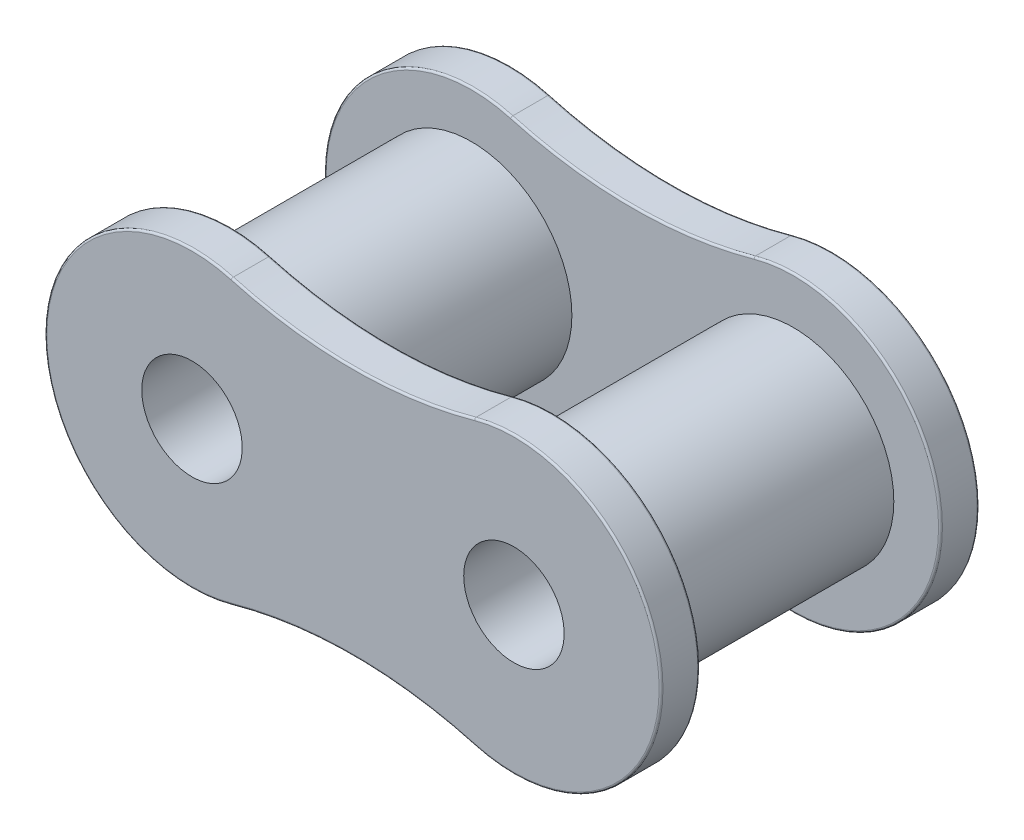
SolidWorks part; units mm, degrees
ref_plane "Front Plane" through (0, 0, 0) normal (0, 0, 1) x (1, 0, 0)
ref_plane "Top Plane" through (0, 0, 0) normal (0, 1, 0) x (1, 0, 0)
ref_plane "Right Plane" through (0, 0, 0) normal (1, 0, 0) x (0, 0, -1)
sketch "Sketch2" plane through (0, 0, 0) normal (0, 0, 1) x (1, 0, 0)
  line L0 (-6.35, 0) -> (6.35, 0) construction
  line L1 (0, -4.9333) -> (0, 4.9333) construction
  circle A0 centre (-6.35, 0) radius 1.9812
  circle A1 centre (-6.35, 0) radius 3.9624
  circle A2 centre (-6.35, 0) radius 5.8039
  circle A11 centre (6.35, 0) radius 1.9812
  circle A12 centre (6.35, 0) radius 3.9624
  circle A13 centre (6.35, 0) radius 5.8039
  point P3 (0, 0)
  point P4 (0, 0)
  point P8 (0, 0)
  point P18 (0, 0)
  point P21 (0, 4.9333)
  point P22 (0, -4.9333)
  point P23 (0, 0)
  dimension "D1" = 11.6078
  dimension "D2" = 3.9624
  dimension "D3" = 7.9248
  dimension "D4" = 12.7
  dimension "D5" = 9.8666
extrude "Boss-Extrude1" add sketch "Sketch2" against normal blind 10 from offset 5.5118 contours A1 A0 | A12 A11 region at (-10.2003, 0, 0) region at (2.4997, 0, 0)
fillet "Fillet1" radius 0.1585 2 edges at (-2.3876, 0, -4.4882) (-2.3876, 0, 5.5118)
fillet "Fillet2" radius 0.1585 2 edges at (10.3124, 0, -4.4882) (10.3124, 0, 5.5118)
sketch "Sketch3" plane through (0, 0, 0) normal (0, 0, 1) x (1, 0, 0)
  line L0 (-6.35, 0) -> (6.35, 0) construction
  line L1 (0, -4.9333) -> (0, 4.9333) construction
  arc A2 (-4.7879, 5.5897) -> (-4.7879, -5.5897) centre (-6.35, 0) ccw
  arc A9 (4.7879, 5.5897) -> (-4.7879, 5.5897) centre (0, 22.723) cw
  arc A10 (4.7879, -5.5897) -> (-4.7879, -5.5897) centre (0, -22.723) ccw
  arc A13 (4.7879, 5.5897) -> (4.7879, -5.5897) centre (6.35, 0) cw
  circle A14 centre (6.35, 0) radius 1.9812 construction
  circle A15 centre (-6.35, 0) radius 1.9812 construction
  circle A16 centre (6.35, 0) radius 1.9812
  circle A17 centre (-6.35, 0) radius 1.9812
  point P4 (0, 0)
  point P8 (0, 0)
  point P14 (0, 4.9333)
  point P15 (0, -4.9333)
  dimension "D1" = 11.6078
  dimension "D4" = 12.7
  dimension "D2" = 9.8666
extrude "Boss-Extrude2" add sketch "Sketch3" along normal blind 1.524 from surface starting at face at (-2.5461, 0, 5.5118)
extrude "Boss-Extrude3" add sketch "Sketch3<3>" along normal blind 1.524 from offset 5.5118 offset against normal yes
sketch "Sketch3<3>" plane through (0, 0, 0) normal (0, 0, 1) x (1, 0, 0) same geometry as "Sketch3"
sketch "Sketch4" plane through (0, 0, 0) normal (0, 0, 1) x (1, 0, 0)
  circle A0 centre (6.35, 0) radius 1.9812 construction
  circle A1 centre (-6.35, 0) radius 1.9812 construction
  circle A2 centre (6.35, 0) radius 1.9812
  circle A3 centre (-6.35, 0) radius 1.9812
  circle A4 centre (-6.35, 0) radius 2.5756
  circle A5 centre (6.35, 0) radius 2.5756
  dimension "D1" = 5.1511
extrude "Cut-Extrude1" cut sketch "Sketch4" against normal through all both and the other way through all
fillet "Fillet3" radius 0.0762 16 edges at (0, 4.9333, -5.5118) (12.1539, 0, -5.5118) (0, -4.9333, -5.5118) (0, 4.9333, -3.9878) (12.1539, 0, -3.9878) (0, -4.9333, -3.9878) (-12.1539, 0, 5.5118) (0, -4.9333, 5.5118) (12.1539, 0, 5.5118) (0, 4.9333, 7.0358) (12.1539, 0, 7.0358) (0, -4.9333, 7.0358) (-12.1539, 0, -5.5118) (-12.1539, 0, -3.9878) (0, 4.9333, 5.5118) (-12.1539, 0, 7.0358)
extrude "Boss-Extrude4" add sketch "Sketch4<2>" along normal through all from surface starting at face at (0, 0, -5.5118)
sketch "Sketch4<2>" plane through (0, 0, 0) normal (0, 0, 1) x (1, 0, 0) same geometry as "Sketch4"
equation "\"H\"= 0.457in"
equation "\"Roller Diameter\"= 0.312in"
equation "\"Pin Diameter\"= 0.156in"
equation "\"Pitch\"= 0.5in"
equation "\"D4@Sketch2\"=\"Pitch\""
equation "\"D1@Sketch2\"=\"H\""
equation "\"D3@Sketch2\"=\"Roller Diameter\""
equation "\"D2@Sketch2\"=\"Pin Diameter\""
equation "\"D5@Sketch2\"=\"H\"*0.85"
equation "\"D1@Fillet1\"=\"Roller Diameter\"*0.02"
equation "\"D1@Fillet2\"=\"Roller Diameter\"*0.02"
equation "\"D2@Sketch3\"=\"H\"*0.85"
equation "\"Roller Width\"= 0.313in"
equation "\"T\"= 0.060in"
equation "\"T1\"= 0.060in"
equation "\"D3\"= 0.002in"
equation "\"D1@Boss-Extrude2\"=\"T\""
equation "\"D1@Boss-Extrude3\"=\"T\""
equation "\"D1@Sketch4\"=\"Pin Diameter\"*1.3"
equation "\"D1@Fillet3\"=\"T\"*0.05"
equation "\"D1@Chamfer1\"=\"Pin Diameter\"*0.05"
